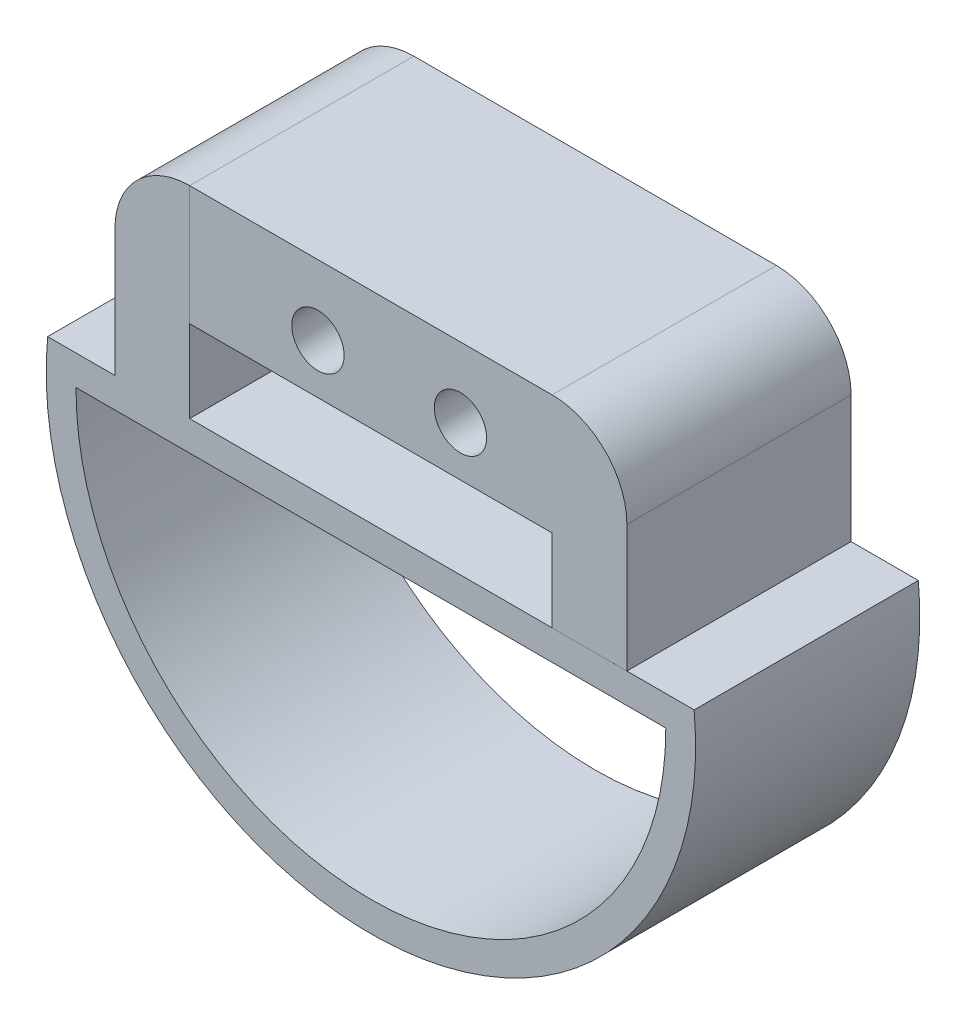
SolidWorks part; units mm, degrees
material "PVC Rigid"
ref_plane "Front Plane" through (0, 0, 0) normal (0, 0, 1) x (1, 0, 0)
ref_plane "Top Plane" through (0, 0, 0) normal (0, 1, 0) x (1, 0, 0)
ref_plane "Right Plane" through (0, 0, 0) normal (1, 0, 0) x (0, 0, -1)
sketch "Sketch1" plane through (0, 0, 0) normal (0, 0, 1) x (1, 0, 0)
  line L0 (-21.6264, 2.0676) -> (21.6264, 2.0676)
  line L1 (18.013, -2.8603) -> (-18.013, -2.8603)
  arc A0 (21.6264, 2.0676) -> (-21.6264, 2.0676) centre (0, 0) cw
  arc A1 (-18.013, -2.8603) -> (18.013, -2.8603) centre (0, 0) ccw
  dimension "D1" = 36.0261
  dimension "1" = 43.2528
extrude "Boss-Extrude3" add sketch "Sketch1" along normal blind 15 and the other way blind 0.0001
sketch "Sketch30" plane through (0, 0, 15) normal (0, 0, 1) x (1, 0, 0)
  line L0 (-19.7299, 0.0676) -> (19.7299, 0.0676)
  line L1 (21.6264, 2.0676) -> (-21.6264, 2.0676) construction
  arc A0 (19.7299, 0.0676) -> (-19.7299, 0.0676) centre (0, 0) cw
  dimension "D2" = 19.73
  dimension "D1" = 2
extrude "Cut-Extrude13" cut sketch "Sketch30" against normal through all
sketch "Sketch31" plane through (0, 2.0676, 0) normal (0, 1, 0) x (1, 0, 0)
  line L0 (21.6264, 0.0001) -> (21.6264, -15) construction
  line L1 (17.1264, -14.9999) -> (12.1264, -14.9999)
  line L2 (17.1264, -14.9999) -> (17.1264, 0.0001)
  line L3 (17.1264, 0.0001) -> (12.1264, 0.0001)
  line L4 (12.1264, -14.9999) -> (12.1264, 0.0001)
  line L5 (17.1264, -14.9999) -> (12.1264, 0.0001) construction
  line L6 (17.1264, 0.0001) -> (12.1264, -14.9999) construction
  line L7 (21.6264, 0.0001) -> (-21.6264, 0.0001) construction
  point P0 (14.6264, -7.4999)
  dimension "D1" = 15
  dimension "D2" = 5
  dimension "D3" = 7
sketch "Sketch32" plane through (0, 2.0676, 0) normal (0, 1, 0) x (1, 0, 0)
  line L0 (17.1264, 0.0001) -> (12.1264, 0.0001) construction
  line L1 (-12.1264, -15) -> (-17.1264, -15)
  line L2 (-12.1264, -15) -> (-12.1264, 0.0001)
  line L3 (-12.1264, 0.0001) -> (-17.1264, 0.0001)
  line L4 (-17.1264, -15) -> (-17.1264, 0.0001)
  line L5 (-12.1264, -15) -> (-17.1264, 0.0001) construction
  line L6 (-12.1264, 0.0001) -> (-17.1264, -15) construction
  line L10 (17.1264, -14.9999) -> (17.1264, 0.0001) construction
  line L11 (21.6264, -15) -> (-21.6264, -15) construction
  line L12 (21.6264, 0.0001) -> (-21.6264, 0.0001) construction
  line L13 (-21.6264, 0.0001) -> (-21.6264, -15) construction
  point P0 (-14.6264, -7.4999)
  dimension "D1" = 7
extrude "Boss-Extrude4" add sketch "Sketch31" along normal blind 13.5
extrude "Boss-Extrude5" add sketch "Sketch32" along normal blind 13.5
sketch "Sketch33" plane through (12.1264, 0, 0) normal (-1, 0, 0) x (0, 0, 1)
  line L0 (-0.0001, 15.5676) -> (14.9999, 15.5676) construction
  line L1 (-0.0001, 15.5676) -> (14.9999, 15.5676)
  line L2 (-0.0001, 15.5676) -> (-0.0001, 7.5676)
  line L3 (-0.0001, 7.5676) -> (14.9999, 7.5676)
  line L4 (14.9999, 15.5676) -> (14.9999, 7.5676)
  line L5 (-0.0001, 15.5676) -> (14.9999, 7.5676) construction
  line L6 (-0.0001, 7.5676) -> (14.9999, 15.5676) construction
  line L7 (14.9999, 15.5676) -> (14.9999, 2.0676) construction
  line L8 (-0.0001, 15.5676) -> (-0.0001, 2.0676) construction
  point P0 (7.4999, 11.5676)
  dimension "D1" = 8
extrude "Boss-Extrude6" add sketch "Sketch33" along normal up to next
sketch "Sketch34" plane through (0.2551, 0, -0.0001) normal (0, 0, -1) x (-1, 0, 0)
  circle A0 centre (-5.7366, 10.8857) radius 1.75
  circle A1 centre (3.7956, 10.8857) radius 1.75
  point P2 (0, 0)
  point P5 (0, 0)
  point P6 (6.6509, 11.0433)
  point P7 (0, 0)
  point P8 (0, 0)
  point P9 (-6.3961, 11.0857)
  point P10 (-5.7366, 10.8857)
  dimension "D1" = 3.5
  dimension "D2" = 3.5
extrude "Cut-Extrude15" cut sketch "Sketch34" against normal up to next contours A1
extrude "Cut-Extrude16" cut sketch "Sketch34<4>" against normal up to next (15 mm away)
sketch "Sketch34<4>" plane through (0.2551, 0, -0.0001) normal (0, 0, -1) x (-1, 0, 0) same geometry as "Sketch34"
fillet "Fillet1" radius 5 1 edges at (17.1264, 15.5676, 7.4999)
fillet "Fillet2" radius 5 1 edges at (-17.1264, 15.5676, 7.5)
